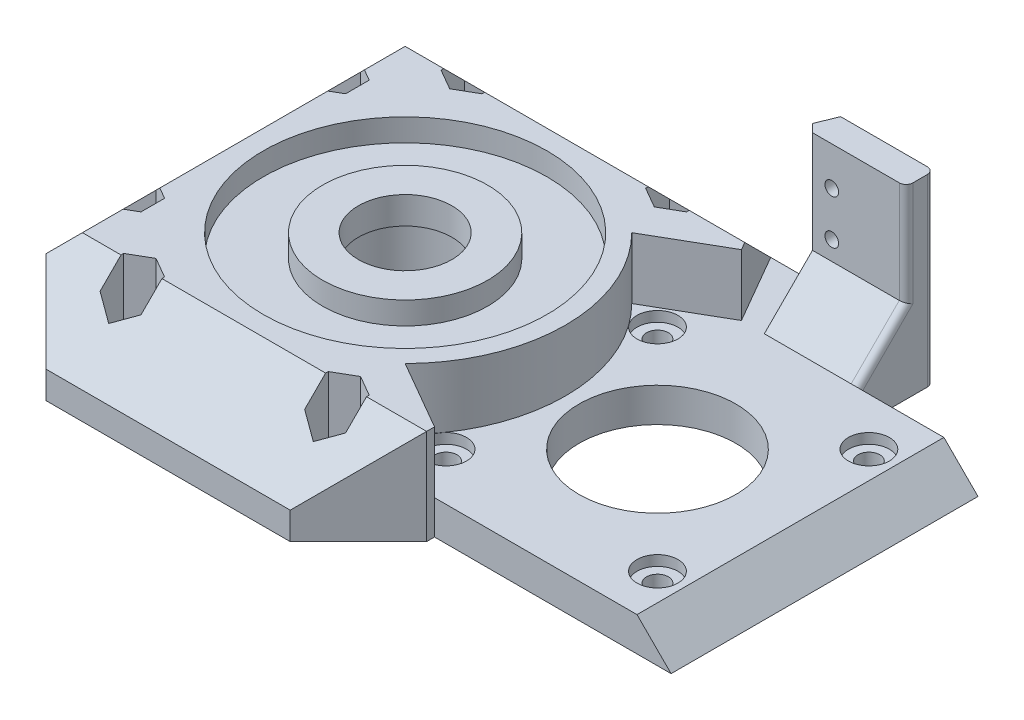
SolidWorks part; units mm, degrees
ref_plane "Front Plane" through (0, 0, 0) normal (0, 0, 1) x (1, 0, 0)
ref_plane "Top Plane" through (0, 0, 0) normal (0, 1, 0) x (1, 0, 0)
ref_plane "Right Plane" through (0, 0, 0) normal (1, 0, 0) x (0, 0, -1)
sketch "Sketch1" plane through (0, 0, 0) normal (0, 1, 0) x (1, 0, 0)
  line L0 (0, 84.8951) -> (0, -74.088) construction
  line L1 (-191.8114, 0) -> (50.4914, 0) construction
  line L2 (24.5, 22.5) -> (24.5, -22.5)
  line L3 (-15.5, 15.5) -> (15.5, 15.5) construction
  line L4 (-15.5, 15.5) -> (-15.5, -15.5) construction
  line L5 (-15.5, -15.5) -> (15.5, -15.5) construction
  line L6 (15.5, 15.5) -> (15.5, -15.5) construction
  line L7 (-15.5, 15.5) -> (15.5, -15.5) construction
  line L8 (-15.5, -15.5) -> (15.5, 15.5) construction
  line L11 (-70.66, 33.66) -> (-70.66, -33.66)
  line L12 (-37, 51.9127) -> (-37, -47.2452) construction
  line L13 (-70.66, -33.66) -> (-10.19, -33.66)
  line L14 (-10.19, -33.66) -> (-10.19, -22.5)
  line L15 (-10.19, -22.5) -> (24.5, -22.5)
  line L16 (-70.66, 33.66) -> (6.9, 33.66)
  line L17 (6.9, 33.66) -> (6.9, 22.5)
  line L18 (6.9, 22.5) -> (24.5, 22.5)
  circle A0 centre (0, 0) radius 11.5
  circle A1 centre (15.5, 15.5) radius 1.6
  circle A2 centre (15.5, -15.5) radius 1.6
  circle A3 centre (-15.5, -15.5) radius 1.6
  circle A4 centre (-15.5, 15.5) radius 1.6
  point P20 (-70.66, 0)
  dimension "D1" = 23
  dimension "D3" = 3.2
  dimension "D4" = 3.2
  dimension "D5" = 3.2
  dimension "D6" = 3.2
  dimension "D2" = 31
  dimension "D7" = 95.16
  dimension "D8" = 24.5
  dimension "D9" = 45
  dimension "D10" = 22.5
  dimension "D11" = 37
  dimension "D12" = 67.32
  dimension "D13" = 60.47
  dimension "D14" = 77.56
extrude "Boss-Extrude1" add sketch "Sketch1" along normal blind 5
sketch "Sketch2" plane through (0, 5, 0) normal (0, 1, 0) x (1, 0, 0)
  line L0 (-191.8114, 0) -> (50.4914, 0) construction
  line L1 (-37, 51.9127) -> (-37, -47.2452) construction
  line L2 (-10.19, -22.5) -> (-20.3818, -16.6158)
  line L3 (-10.19, -22.5) -> (-10.19, -33.66)
  line L4 (-10.19, -33.66) -> (-70.66, -33.66)
  line L5 (-70.66, -33.66) -> (-70.66, 33.66)
  line L6 (-94.9981, 0) -> (32.9832, 0) construction
  line L8 (-10.19, 22.5) -> (-20.3818, 16.6158)
  line L9 (-10.19, 22.5) -> (-16.6332, 33.66)
  line L10 (-70.66, 33.66) -> (6.9, 33.66) construction
  line L11 (-16.6332, 33.66) -> (-70.66, 33.66)
  circle A0 centre (-37, 0) radius 23.5
  line M4 (6.9, 33.66) -> (-70.66, 33.66)
  line M5 (-70.66, 33.66) -> (-70.66, -33.66)
  line M6 (-70.66, -33.66) -> (-10.19, -33.66)
  line M7 (-10.19, -33.66) -> (-10.19, -22.5)
  dimension "D1" = 47
  dimension "D2" = 30
extrude "Boss-Extrude2" add sketch "Sketch2" along normal blind 9 contours L6 L5 L2 A0 M6 M7 | L6 A0 | A0 L6 | L6 A0 L8 L9 M5 M4 region at (-46.3769, 5, 23.0498) region at (-37, 5, 9.9737) region at (-37, 5, -9.9737) region at (-47.5869, 5, -22.8049)
sketch "Sketch3" plane through (0, 14, 0) normal (0, 1, 0) x (1, 0, 0)
  line L0 (-83.8486, 0) -> (29.3929, 0) construction
  line L1 (-37, 35.9931) -> (-37, -40.7398) construction
  circle A0 centre (-37, 0) radius 12.1
  circle A1 centre (-37, 0) radius 20.8
  dimension "D1" = 24.2
  dimension "D2" = 41.6
extrude "Cut-Extrude1" cut sketch "Sketch3" against normal blind 3.3
sketch "Sketch4" plane through (0, 14, 0) normal (0, 1, 0) x (1, 0, 0)
  circle A0 centre (-37, 0) radius 6.85
  dimension "D1" = 13.7
extrude "Cut-Extrude2" cut sketch "Sketch4" against normal blind 4
sketch "Sketch5" plane through (0, 0, 0) normal (0, -1, 0) x (1, 0, 0)
  circle A0 centre (-37, 0) radius 7.85
  dimension "D1" = 15.7
extrude "Cut-Extrude3" cut sketch "Sketch5" against normal up to surface (10 mm away) up to face at (-37, 10, 6.85)
sketch "Sketch6" plane through (0, 14, 0) normal (0, 1, 0) x (1, 0, 0)
  line L0 (-79.8063, 0) -> (35.8388, 0) construction
  line L1 (-37, 0) -> (-37, 40.9883) construction
  line L2 (-37, 0) -> (-37, -43.3138) construction
  line L3 (-79.8063, 25) -> (20.7848, 25) construction
  line L4 (-55, 26.7321) -> (-52, 28.4641)
  line L5 (-22, 28.4641) -> (-25, 26.7321)
  line L6 (-25, 26.7321) -> (-25, 23.2679)
  line L7 (-25, 23.2679) -> (-22, 21.5359)
  line L8 (-22, 21.5359) -> (-19, 23.2679)
  line L9 (-19, 23.2679) -> (-19, 26.7321)
  line L10 (-19, 26.7321) -> (-22, 28.4641)
  line L11 (-55, 23.2679) -> (-55, 26.7321)
  line L12 (-52, 28.4641) -> (-49, 26.7321)
  line L13 (-49, 23.2679) -> (-52, 21.5359)
  line L14 (-49, 26.7321) -> (-49, 23.2679)
  line L15 (-52, 21.5359) -> (-55, 23.2679)
  line L16 (-52, -21.5359) -> (-55, -23.2679)
  line L17 (-49, -26.7321) -> (-49, -23.2679)
  line L18 (-49, -23.2679) -> (-52, -21.5359)
  line L19 (-52, -28.4641) -> (-49, -26.7321)
  line L20 (-55, -23.2679) -> (-55, -26.7321)
  line L21 (-55, -26.7321) -> (-52, -28.4641)
  line L22 (-19, -26.7321) -> (-22, -28.4641)
  line L23 (-19, -23.2679) -> (-19, -26.7321)
  line L24 (-22, -21.5359) -> (-19, -23.2679)
  line L25 (-25, -23.2679) -> (-22, -21.5359)
  line L26 (-25, -26.7321) -> (-25, -23.2679)
  line L27 (-22, -28.4641) -> (-25, -26.7321)
  line L28 (-62, 40.9883) -> (-62, -40.4134) construction
  line L29 (-65, -13.2679) -> (-62, -11.5359)
  line L30 (-62, 11.5359) -> (-59, 13.2679)
  line L31 (-59, 13.2679) -> (-59, 16.7321)
  line L32 (-59, 16.7321) -> (-62, 18.4641)
  line L33 (-62, 18.4641) -> (-65, 16.7321)
  line L34 (-65, 16.7321) -> (-65, 13.2679)
  line L35 (-65, 13.2679) -> (-62, 11.5359)
  line L36 (-65, -16.7321) -> (-65, -13.2679)
  line L37 (-62, -18.4641) -> (-65, -16.7321)
  line L38 (-59, -16.7321) -> (-62, -18.4641)
  line L39 (-59, -13.2679) -> (-59, -16.7321)
  line L40 (-62, -11.5359) -> (-59, -13.2679)
  circle A0 centre (-22, 25) radius 3 construction
  circle A1 centre (-52, 25) radius 3 construction
  circle A2 centre (-52, -25) radius 3 construction
  circle A3 centre (-22, -25) radius 3 construction
  circle A4 centre (-62, 15) radius 3 construction
  circle A5 centre (-62, -15) radius 3 construction
  dimension "D3" = 6
  dimension "D5" = 6
  dimension "D1" = 25
  dimension "D2" = 15
  dimension "D4" = 25
  dimension "D6" = 15
extrude "Cut-Extrude4" cut sketch "Sketch6" against normal blind 10
sketch "Sketch7" plane through (0, 4, 0) normal (0, 1, 0) x (1, 0, 0)
  circle A0 centre (-62, -15) radius 2.15
  circle A1 centre (-52, -25) radius 2.15
  circle A2 centre (-22, -25) radius 2.15
  circle A3 centre (-62, 15) radius 2.15
  circle A4 centre (-52, 25) radius 2.15
  circle A5 centre (-22, 25) radius 2.15
  dimension "D1" = 4.3
  dimension "D2" = 4.3
  dimension "D3" = 4.3
  dimension "D4" = 4.3
  dimension "D5" = 4.3
  dimension "D6" = 4.3
extrude "Cut-Extrude5" cut sketch "Sketch7" against normal through all
chamfer "Chamfer1" distance 10 angle 45 4 edges at (-10.19, 7, 33.66) (-43.6466, 14, -33.66) (-40.425, 14, 33.66) (-70.66, 14, 0)
chamfer "Chamfer2" distance 14.66 angle 45 2 edges at (-70.66, 2, 33.66) (-70.66, 2, -33.66)
chamfer "Chamfer3" distance 5 angle 45 1 edges at (24.5, 5, 0)
sketch "Sketch8" plane through (0, 5, 0) normal (0, 1, 0) x (1, 0, 0)
  circle A0 centre (15.5, 15.5) radius 3
  circle A1 centre (-15.5, 15.5) radius 3
  circle A2 centre (-15.5, -15.5) radius 3
  circle A3 centre (15.5, -15.5) radius 3
  dimension "D1" = 6
  dimension "D2" = 6
  dimension "D3" = 6
  dimension "D4" = 6
extrude "Cut-Extrude6" cut sketch "Sketch8" against normal blind 1.5
sketch "Sketch9" plane through (0, 5, 0) normal (0, 1, 0) x (1, 0, 0)
  line L0 (6.9, 33.66) -> (6.9, 29.56)
  line L1 (6.9, 22.5) -> (6.9, 32.66) construction
  line L2 (6.9, 29.56) -> (-6.8, 29.56)
  line L3 (-6.8, 29.56) -> (-7.9959, 30.7559)
  line L4 (-7.9959, 30.7559) -> (-6.8, 33.66)
  line L5 (-56, 33.66) -> (6.9, 33.66) construction
  line L6 (-6.8, 33.66) -> (6.9, 33.66)
  dimension "D1" = 4.1
  dimension "D2" = 13.7
extrude "Boss-Extrude3" add sketch "Sketch9" along normal blind 22 and the other way blind 1.5
sketch "Sketch10" plane through (6.9, 0, 0) normal (1, 0, 0) x (0, 0, -1)
  line L0 (22.5, 5) -> (29.56, 12.06)
  line L1 (29.56, 27) -> (29.56, 5) construction
  line L2 (22.5, 5) -> (32.66, 5) construction
  line L3 (22.5, 5) -> (29.56, 5)
  line L4 (29.56, 5) -> (29.56, 12.06)
  dimension "D1" = 45
extrude "Boss-Extrude4" add sketch "Sketch10" against normal blind 13.73 contours L0 L4 L3
sketch "Sketch12" plane through (0, 0, -29.56) normal (0, 0, 1) x (1, 0, 0)
  line L0 (-4, 36.5564) -> (-4, 8.4542) construction
  line L1 (-6.83, 5) -> (6.9, 5) construction
  circle A0 centre (-4, 21.35) radius 1
  circle A1 centre (-4, 14.85) radius 1
  dimension "D2" = 2
  dimension "D3" = 2
  dimension "D1" = 4
  dimension "D4" = 6.5
  dimension "D5" = 16.35
extrude "Cut-Extrude7" cut sketch "Sketch12" against normal blind 13.73
sketch "Sketch13" plane through (0, 0, -33.66) normal (0, 0, -1) x (-1, 0, 0)
  circle A0 centre (4, 14.85) radius 2.5
  circle A1 centre (4, 21.35) radius 2.5
  dimension "D1" = 5
  dimension "D2" = 5
extrude "Cut-Extrude8" cut sketch "Sketch13" against normal blind 1.5
fillet "Fillet1" radius 1 3 edges at (6.9, 8.53, -26.03) (6.9, 19.53, -29.56) (6.9, 13.5, -33.66)
